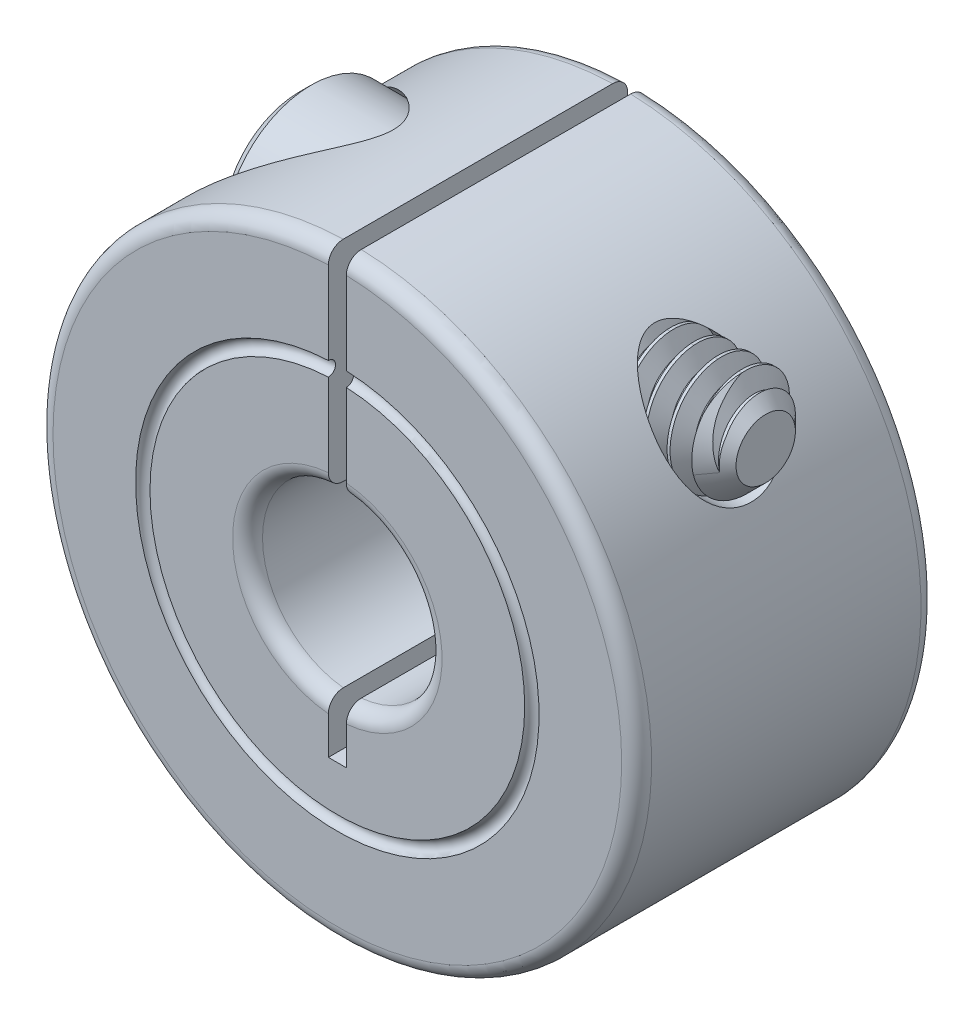
SolidWorks part; units mm, degrees
ref_plane "Front Plane" through (0, 0, 0) normal (0, 0, 1) x (1, 0, 0)
ref_plane "Top Plane" through (0, 0, 0) normal (0, 1, 0) x (1, 0, 0)
ref_plane "Right Plane" through (0, 0, 0) normal (1, 0, 0) x (0, 0, -1)
sketch "Sketch1" plane through (0, 0, 0) normal (0, 0, 1) x (1, 0, 0)
  line L0 (-0.2381, 2.3693) -> (-0.2381, 7.9339)
  line L2 (0.2381, 2.3693) -> (0.2381, 7.9339)
  line L3 (0, 0) -> (0, 2.3693) construction
  line L4 (0.2381, 2.3693) -> (-0.2381, 2.3693) construction
  line L5 (0, -7.9375) -> (0, -2.3813) construction
  line L6 (0, -2.3813) -> (0, -5.1594) construction
  line L7 (-0.2381, -2.3693) -> (-0.2381, -3.7703)
  line L8 (-0.2381, -3.7703) -> (0.2381, -3.7703)
  line L9 (0.2381, -2.3693) -> (0.2381, -3.7703)
  line L10 (-0.2381, 5.1516) -> (0.2381, 5.1516) construction
  circle A0 centre (0, 0) radius 7.9375 construction
  circle A1 centre (0, 0) radius 2.3813 construction
  arc A3 (-0.2381, 7.9339) -> (0.2381, 7.9339) centre (0, 0) ccw
  arc A4 (0.2381, -2.3693) -> (0.2381, 2.3693) centre (0, 0) ccw
  arc A5 (-0.2381, 2.3693) -> (-0.2381, -2.3693) centre (0, 0) ccw
  point P4 (7.9375, 0)
  point P5 (-7.9375, 0)
  point P19 (0, -3.7703)
  dimension "Bore Dia" = 4.7625
  dimension "OD" = 15.875
  dimension "Separation" = 0.4763
extrude "Extrude1" add sketch "Sketch1" along normal mid plane 7.9375
fillet "Fillet1" radius 0.3969 6 edges at (0, -7.9375, -3.9688) (0, -7.9375, 3.9688) (-2.3813, 0, 3.9688) (-2.3813, 0, -3.9688) (2.3812, 0, 3.9688) (2.3812, 0, -3.9688)
sketch "Sketch2" plane through (0, 0, 0) normal (0, 1, 0) x (1, 0, 0)
  line L0 (0, 0) -> (-2.3813, 0) construction
  line L1 (-2.3813, 0) -> (-7.9375, 0) construction
  line L2 (-5.1594, 3.9688) -> (-5.1594, -3.9688) construction
  line L3 (7.5406, 3.9688) -> (-7.5406, 3.9688) construction
  line L4 (-7.5406, -3.9688) -> (7.5406, -3.9688) construction
  line L5 (-7.9375, 3.5719) -> (-7.9375, -3.5719) construction
  line L6 (-2.3813, 3.5719) -> (-2.3813, -3.5719) construction
  line L8 (-5.3499, -3.9688) -> (-4.9689, -3.9688)
  line L9 (0, 3.9688) -> (0, -3.9688) construction
  line L10 (-0.2381, 3.9688) -> (-2.7781, 3.9688) construction
  arc A1 (-4.9689, -3.9688) -> (-5.3499, -3.9688) centre (-5.1594, -3.9688) ccw
  point P1 (-5.1594, 0)
  dimension "D2" = 0.1905
revolve "Cut-Revolve1" cut sketch "Sketch2" angle 360 about L9
sketch "Sketch3" plane through (0, 0, 0) normal (0, 0, 1) x (1, 0, 0)
  line L0 (7.9375, 5.1516) -> (-7.9375, 5.1516)
  line L1 (-7.9375, 5.1516) -> (-7.9375, 2.764)
  line L2 (-7.9375, 2.764) -> (-2.1336, 2.764)
  line L4 (-2.1336, 2.764) -> (-2.1336, 3.7292)
  line L7 (-2.1336, 3.7292) -> (7.9375, 3.7292)
  line L8 (7.9375, 3.7292) -> (7.9375, 5.1516)
  line L9 (-7.9375, 5.1516) -> (-10.3251, 5.1516) construction
  line L10 (-0.2381, 5.1516) -> (0.2381, 5.1516) construction
  dimension "D4" = 4.7752
  dimension "D2" = 2.1336
revolve "Cut-Revolve2" cut sketch "Sketch3" angle 360 about L9
sketch "Sketch4" plane through (0, 0, 0) normal (0, 0, 1) x (1, 0, 0)
  line L0 (-4.9784, 5.1516) -> (-4.9784, 7.4757)
  line L2 (-4.9784, 7.4757) -> (-2.1336, 7.4757)
  line L3 (-2.1336, 7.4757) -> (-2.1336, 6.574)
  line L4 (-2.1336, 6.574) -> (7.3914, 6.574)
  line L5 (-2.1336, 2.764) -> (-2.1336, 3.7292) construction
  line L6 (7.3914, 6.574) -> (7.3914, 5.1516)
  line L7 (-2.1336, 3.7292) -> (7.9375, 3.7292) construction
  line L8 (7.3914, 5.1516) -> (-4.9784, 5.1516)
  line L9 (7.3914, 6.574) -> (7.3914, 3.7292) construction
  line L10 (-4.9784, 5.1516) -> (-7.3025, 5.1516) construction
  line L11 (-7.9375, 5.1516) -> (-10.3251, 5.1516) construction
  dimension "Head Dia" = 4.6482
revolve "Revolve1" add sketch "Sketch4" angle 360 about L8
sketch "Sketch5" plane through (-4.9784, 0, 0) normal (-1, 0, 0) x (0, -1, 0)
  line L1 (-4.4642, -1.1906) -> (-3.7768, 0)
  line L2 (-3.7768, 0) -> (-4.4642, 1.1906)
  line L3 (-4.4642, 1.1906) -> (-5.839, 1.1906)
  line L4 (-5.839, 1.1906) -> (-6.5264, 0)
  line L5 (-6.5264, 0) -> (-5.839, -1.1906)
  line L6 (-5.839, -1.1906) -> (-4.4642, -1.1906)
  circle A0 centre (-5.1516, 0) radius 1.1906 construction
  dimension "Hex" = 2.3813
extrude "Cut-Extrude1" cut sketch "Sketch5" against normal blind 2.3813
chamfer "Chamfer1" distance 0.3175 angle 45 1 edges at (-4.9784, 7.4757, 0)
sketch "Sketch6" plane through (7.3914, 0, 0) normal (1, 0, 0) x (0, 1, 0)
  circle A0 centre (5.1516, 0) radius 1.4224 construction
  circle A1 centre (5.1516, 0) radius 1.4224
  point P3 (6.574, 0)
curve "Helix/Spiral1" pitch 0.635 height 9.525 turns 15 parameters "Height"=9.525, "Pitch"=0.635
sketch "Sketch7" plane through (0, 0, 0) normal (0, 0, 1) x (1, 0, 0)
  line L0 (7.6692, 6.0928) -> (7.3517, 6.6428) construction
  line L1 (7.3517, 6.6428) -> (7.9867, 6.6428) construction
  line L2 (7.9867, 6.6428) -> (7.6692, 6.0928) construction
  line L3 (7.3914, 6.574) -> (7.947, 6.574) construction
  line L4 (7.6295, 6.1616) -> (7.7089, 6.1616)
  line L5 (7.6692, 6.6428) -> (7.6692, 6.574) construction
  line L6 (7.6692, 6.1616) -> (7.6692, 6.0928) construction
  line L7 (7.6295, 6.1616) -> (7.3716, 6.6084)
  line L8 (7.3716, 6.6084) -> (7.9669, 6.6084)
  line L9 (7.9669, 6.6084) -> (7.7089, 6.1616)
  point P10 (7.6692, 6.6084)
  dimension "D1" = 0.635
  dimension "D2" = 0.0794
chamfer "Chamfer2" distance 0.635 angle 45 1 edges at (7.3914, 6.574, 0)
sweep "Cut-Sweep1" cut profiles "Sketch7" path "Helix/Spiral1"
equation "\"D1@Sketch3\" = \"Screw Dia@Sketch3\""
equation "\"D1@Cut-Extrude1\" = \"Hex@Sketch5\""
equation "\"D1@Fillet1\" = \"Width@Extrude1\"*.05"
equation "\"D4@Sketch3\" = \"Head Dia@Sketch4\" + .005"
equation "\"Height@Helix/Spiral1\" = \"Screw Lg@Sketch4\""
equation "\"D1@Sketch7\" = \"Pitch@Helix/Spiral1\""
equation "\"D2@Sketch7\" = \"D1@Sketch7\"/8"
equation "\"D1@Chamfer2\" = \"Pitch@Helix/Spiral1\""
equation "\"Separation@Sketch1\" = \"Bore Dia@Sketch1\"/10"
equation "\"D2@Sketch3\" = \"Screw Dia@Sketch3\"*.750"
